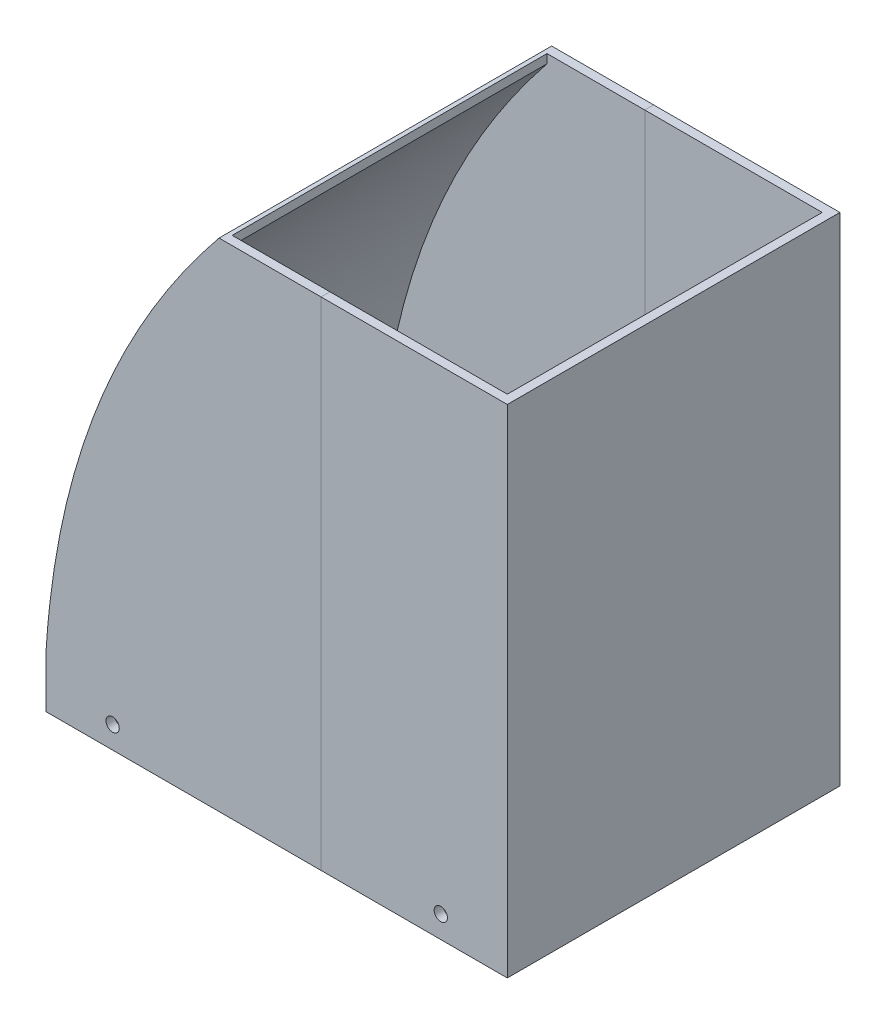
SolidWorks part; units mm, degrees
ref_plane "Front Plane" through (0, 0, 0) normal (0, 0, 1) x (1, 0, 0)
ref_plane "Top Plane" through (0, 0, 0) normal (0, 1, 0) x (1, 0, 0)
ref_plane "Right Plane" through (0, 0, 0) normal (1, 0, 0) x (0, 0, -1)
sketch "Sketch1" plane through (0, 0, 0) normal (0, 1, 0) x (1, 0, 0)
  line L1 (-52, 37.5) -> (52, 37.5)
  line L2 (-52, 37.5) -> (-52, -37.5)
  line L3 (-52, -37.5) -> (52, -37.5)
  line L4 (52, 37.5) -> (52, -37.5)
  line L5 (-52, 37.5) -> (52, -37.5) construction
  line L6 (-52, -37.5) -> (52, 37.5) construction
  point P0 (0, 0)
  dimension "D1" = 75
  dimension "1.4" = 104
extrude "Boss-Extrude2" add sketch "Sketch1" along normal blind 12
sketch "Sketch2" plane through (0, 0, 37.5) normal (0, 0, 1) x (1, 0, 0)
  line L0 (52, 12) -> (52, 112)
  line L1 (52, 112) -> (-13, 112)
  line L2 (52, 12) -> (-52, 12)
  spline S0 degree 2 poles (-13, 112) (-48.4598, 68.3634) (-52, 12) knots 0 0 0 1 1 1
  dimension "D1" = 100
  dimension "D2" = 65
extrude "Boss-Extrude4" add sketch "Sketch2" against normal blind 75
shell "Shell1" thickness 2 removed face at (0, 0, 0)
sketch "Sketch3" plane through (0, 110, 0) normal (0, -1, 0) x (1, 0, 0)
  line L0 (-12.0451, 35.5) -> (-12.0451, -35.5)
  line L1 (-12.0451, -35.5) -> (50, -35.5)
  line L2 (50, -35.5) -> (50, 35.5)
  line L3 (50, 35.5) -> (-12.0451, 35.5)
extrude "Cut-Extrude1" cut sketch "Sketch3" against normal through all
sketch "Sketch4" plane through (0, 0, 37.5) normal (0, 0, 1) x (1, 0, 0)
  line L0 (-52, 5) -> (52, 5) construction
  line L1 (-52, 12) -> (-52, 0) construction
  line L2 (52, 112) -> (52, 0) construction
  line L3 (-52, 0) -> (52, 0) construction
  circle A0 centre (-37, 5) radius 1.5
  circle A1 centre (37, 5) radius 1.5
  dimension "D2" = 3
  dimension "D1" = 5
  dimension "D3" = 15
  dimension "D4" = 15
extrude "Cut-Extrude2" cut sketch "Sketch4" against normal through all
ref_plane "Plane1" through (10, 0, 0) normal (1, 0, 0) x (0, 0, -1)
split "Split1" trim tools "Plane1" bodies to split 105 resulting bodies 106 107
